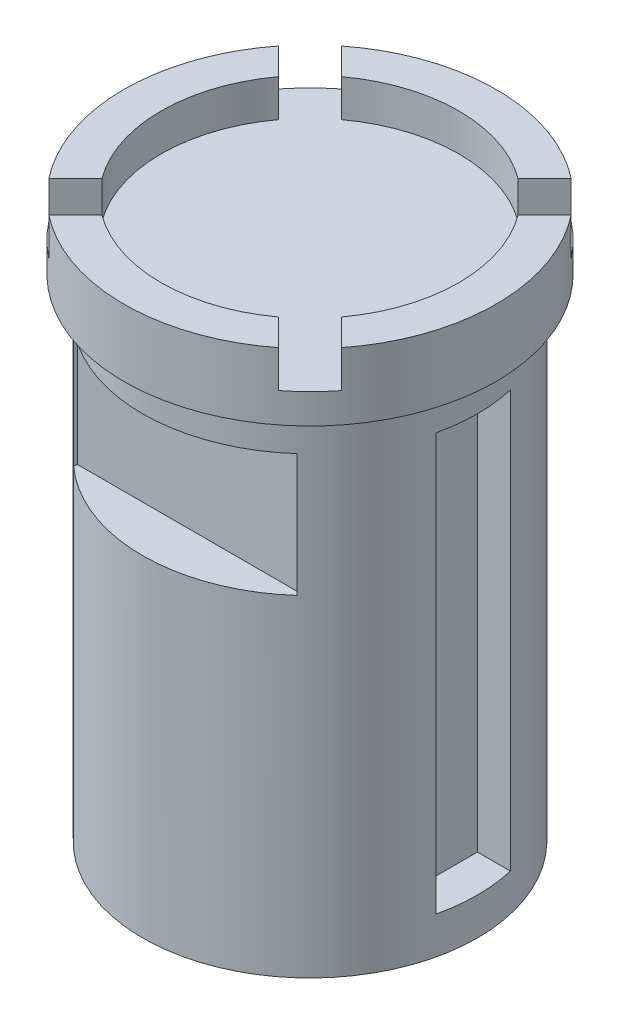
SolidWorks part; units mm, degrees
other "Satellite Body"
ref_plane "Front Plane" through (0, 0, 0) normal (0, 0, 1) x (1, 0, 0)
ref_plane "Top Plane" through (0, 0, 0) normal (0, 1, 0) x (1, 0, 0)
ref_plane "Right Plane" through (0, 0, 0) normal (1, 0, 0) x (0, 0, -1)
sketch "Body Block Sketch" plane through (0, 0, 0) normal (0, 0, 1) x (1, 0, 0)
  line L1 (0, 0) -> (400, 0)
  line L2 (0, 0) -> (0, -1400)
  line L3 (0, -1400) -> (450, -1400)
  line L6 (450, 0) -> (450, -80) construction
  line L9 (500, 0) -> (500, 100)
  line L13 (500, 100) -> (400, 100)
  line L14 (400, 0) -> (400, 100)
  line L15 (400, 0) -> (450, 0) construction
  line L16 (450, 0) -> (400, 0) construction
  line L17 (450, -80) -> (450, -1400)
  line L18 (450, -80) -> (500, -80)
  line L19 (500, 0) -> (500, -80)
  line L21 (400, 0) -> (500, 0) construction
  dimension "D1" = 1400
  dimension "D2" = 500
  dimension "D3" = 50
  dimension "D4" = 100
  dimension "D5" = 100
  dimension "D6" = 80
revolve "Body Block Revolve" add sketch "Body Block Sketch" angle 360 about L2
ref_plane "Surface Feature Start Plane" through (0, -180, 0) normal (0, -1, 0) x (-1, 0, 0)
sketch "Solar Divot Sketch" plane through (0, -180, 0) normal (0, -1, 0) x (-1, 0, 0)
  line L0 (0, 0) -> (-450, 0) construction
  line L1 (-450, 100) -> (-350, 100)
  line L2 (-450, 100) -> (-450, -100)
  line L3 (-450, -100) -> (-350, -100)
  line L4 (-350, 100) -> (-350, -100)
  line L5 (0, -926.423) -> (0, 49073.577) construction
  line L6 (350, 100) -> (350, -100)
  line L7 (450, -100) -> (350, -100)
  line L8 (450, 100) -> (450, -100)
  line L9 (450, 100) -> (350, 100)
  circle A0 centre (0, 0) radius 450 construction
  dimension "D1" = 200
  dimension "D2" = 100
extrude "Solar Divot Cut" cut sketch "Solar Divot Sketch" along normal offset from surface (1120 mm away) 100 up to face at (-450, -1400, 0)
sketch "Misc Bay Sketch" plane through (0, -180, 0) normal (0, -1, 0) x (-1, 0, 0)
  line L0 (0, 0) -> (0, 450) construction
  line L1 (-300, 450) -> (300, 450)
  line L2 (-300, 450) -> (-300, 325.4102)
  line L3 (-300, 325.4102) -> (300, 325.4102)
  line L4 (300, 450) -> (300, 325.4102)
  line L5 (-3000, 0) -> (3000, 0) construction
  line L6 (300, -450) -> (300, -325.4102)
  line L7 (-300, -325.4102) -> (300, -325.4102)
  line L8 (-300, -450) -> (300, -450)
  line L9 (-300, -450) -> (-300, -325.4102)
  circle A0 centre (0, 0) radius 450 construction
  circle A2 centre (0, 0) radius 450 construction
  point P14 (0, 0)
  point P18 (300, 335.4102)
  dimension "D1" = 600
  dimension "D2" = 10
extrude "Misc Bay Cut" cut sketch "Misc Bay Sketch" along normal blind 330
sketch "Launch Adaptor Bay Sketch" plane through (0, -1400, 0) normal (0, -1, 0) x (1, 0, 0)
  circle A2 centre (0, 0) radius 370
  circle A3 centre (0, 0) radius 370
  dimension "D1" = 80
extrude "Launch Adaptor Bay Cut" cut sketch "Launch Adaptor Bay Sketch" against normal blind 40
sketch "Gripper Gap Sketch" plane through (0, 0, 0) normal (0, 1, 0) x (1, 0, 0)
  line L0 (0, 0) -> (0, 500) construction
  line L1 (311.127, 395.9798) -> (395.9798, 311.127)
  line L2 (311.127, 395.9798) -> (-42.4264, 42.4264)
  line L3 (-42.4264, 42.4264) -> (42.4264, -42.4264)
  line L4 (395.9798, 311.127) -> (42.4264, -42.4264)
  line L5 (0, 0) -> (353.5534, 353.5534) construction
  circle A0 centre (0, 0) radius 500 construction
  dimension "D1" = 120
  dimension "D2" = 500
  dimension "D3" = 45
extrude "Gripper Gap Cut" cut sketch "Gripper Gap Sketch" along normal up to surface (100 mm away) up to face at (-400, 100, 0)
pattern_circular "Gripper Gap Cut Propagation" count 4 over 360 about axis through (0, 0, 0) along (0, -1, 0) of "Gripper Gap Cut"
ref_plane "Gripper Lip Midplane" through (0, 50, 0) normal (0, 1, 0) x (1, 0, 0)
sketch "Gripper Gap Midpoint Sketch" plane through (0, 50, 0) normal (0, 1, 0) x (1, 0, 0)
  line L0 (353.5534, 353.5534) -> (282.8427, 282.8427) construction
  line L1 (282.8427, 282.8427) -> (-282.8427, -282.8427) construction
  line L2 (0, 0) -> (353.5534, 353.5534) construction
  line L3 (-282.8427, -282.8427) -> (-353.5534, -353.5534) construction
  line L4 (0, 0) -> (-282.8427, 282.8427) construction
  line L5 (-282.8427, 282.8427) -> (-353.5534, 353.5534) construction
  line L6 (353.5534, -353.5534) -> (282.8427, -282.8427) construction
  line L7 (282.8427, -282.8427) -> (0, 0) construction
  circle A0 centre (0, 0) radius 400 construction
  circle A1 centre (0, 0) radius 500 construction
  circle A2 centre (0, 0) radius 500 construction
  arc A3 (237.2162, 322.069) -> (-237.2162, 322.069) centre (0, 0) ccw construction
  arc A4 (-393.425, 308.5722) -> (-393.425, -308.5722) centre (0, 0) ccw construction
  point P14 (318.1981, 318.1981)
  point P16 (318.1981, -318.1981)
  point P21 (0, 0)
  point P25 (318.1981, -318.1981)
  point P26 (-318.1981, -318.1981)
  point P30 (-318.1981, 318.1981)
  point P31 (0, 0)
  point P32 (0, 0)
  point P33 (0, 0)
  point P34 (0, 0)
